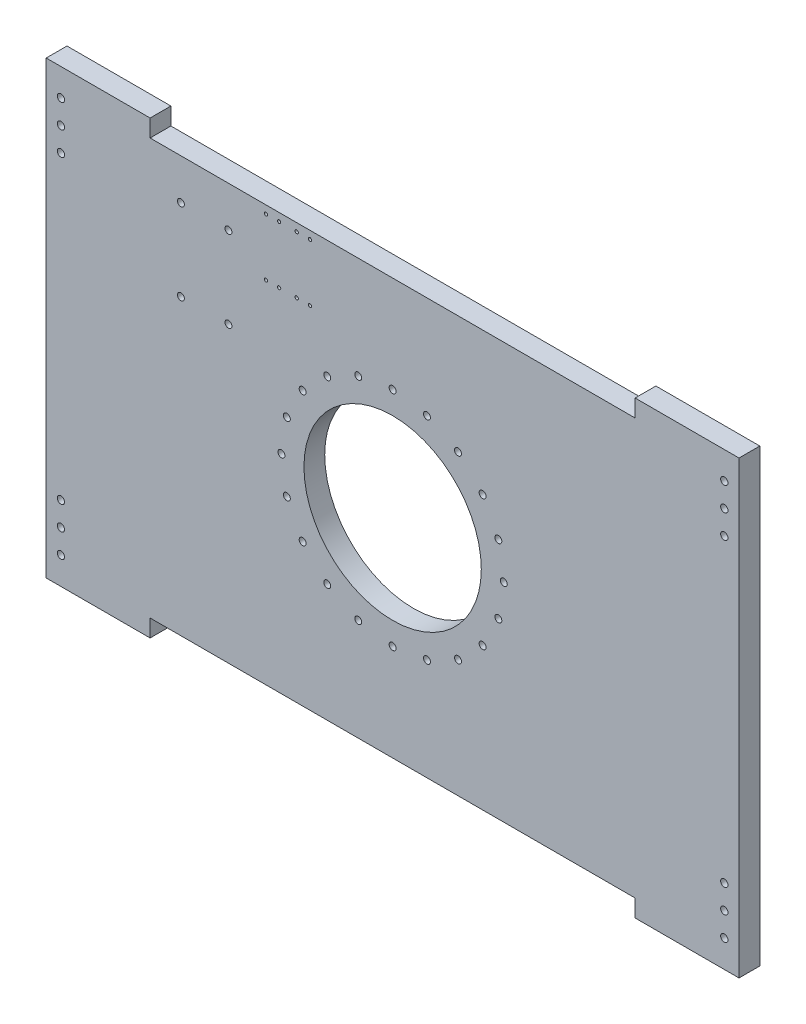
SolidWorks part; units mm, degrees
material "ASTM A36 Acier"
ref_plane "Plan de face" through (0, 0, 0) normal (0, 0, 1) x (1, 0, 0)
ref_plane "Plan de dessus" through (0, 0, 0) normal (0, 1, 0) x (1, 0, 0)
ref_plane "Plan de droite" through (0, 0, 0) normal (1, 0, 0) x (0, 0, -1)
sketch "Esquisse1" plane through (0, 0, 0) normal (0, 0, 1) x (1, 0, 0)
  line L0 (-1000, 1250) -> (-700, 1250)
  line L1 (-700, 1250) -> (-700, 1200)
  line L2 (-700, 1200) -> (700, 1200)
  line L3 (700, 1200) -> (700, 1250)
  line L4 (700, 1250) -> (1000, 1250)
  line L5 (1000, 1250) -> (1000, -50)
  line L6 (1000, -50) -> (700, -50)
  line L7 (700, -50) -> (700, 0)
  line L8 (700, 0) -> (-700, 0)
  line L9 (-700, 0) -> (-700, -50)
  line L10 (-700, -50) -> (-1000, -50)
  line L11 (-1000, -50) -> (-1000, 1250)
  point P15 (0, 0)
  dimension "D1" = 2000
  dimension "D2" = 50
  dimension "D4" = 300
  dimension "D5" = 300
  dimension "D6" = 300
  dimension "D7" = 300
  dimension "D8" = 1200
  dimension "D9" = 50
  dimension "D10" = 1400
extrude "Boss.-Extru.1" add sketch "Esquisse1" along normal blind 60
sketch "Esquisse2" plane through (0, 0, 60) normal (0, 0, 1) x (1, 0, 0)
  line L0 (700, -50) -> (1000, -50) construction
  circle A0 centre (0, 600) radius 256
  dimension "D1" = 512
  dimension "D2" = 650
extrude "Enlèv. mat.-Extru.1" cut sketch "Esquisse2" against normal through all
sketch "Esquisse4" plane through (0, 0, 0) normal (1, 0, 0) x (0, 0, -1)
  line L0 (0, 600) -> (1429.3387, 600) construction
  dimension "D1" = 600
sketch "Esquisse5" plane through (0, 0, 0) normal (0, 0, 1) x (1, 0, 0)
  circle A0 centre (0, 921) radius 10
  circle A1 centre (0, 600) radius 256 construction
  dimension "D1" = 20
  dimension "D2" = 321
extrude "Enlèv. mat.-Extru.3" cut sketch "Esquisse5" along normal through all
pattern_circular "Répétition circulaire1" count 20 every 18 about axis through (0, 600, 0) along (0, 0, -1) of "Enlèv. mat.-Extru.3"
ref_plane "Plan1" through (0, 0, 0) normal (0, 0, -1) x (-1, 0, 0)
sketch "Esquisse6" plane through (0, 0, 0) normal (0, 0, -1) x (-1, 0, 0)
  line L0 (1000, -50) -> (1000, 1250) construction
  line L1 (-1000, -50) -> (-1000, 1250) construction
  line L3 (0, 1100) -> (0, 0) construction
  line L5 (-700, -50) -> (-1000, -50) construction
  line L6 (994.9902, 600) -> (-1002.7622, 600) construction
  line L8 (700, 1200) -> (-700, 1200) construction
  circle A1 centre (-957.5, 28.75) radius 10.5
  circle A8 centre (-957.5, 1171.25) radius 10.5
  circle A9 centre (957.5, 1171.25) radius 10.5
  circle A14 centre (957.5, 28.75) radius 10.5
  circle A15 centre (-957.5, 97.5) radius 10.5
  circle A16 centre (-957.5, 166.25) radius 10.5
  circle A17 centre (-957.5, 1033.75) radius 10.5
  circle A18 centre (-957.5, 1102.5) radius 10.5
  circle A19 centre (957.5, 97.5) radius 10.5
  circle A20 centre (957.5, 166.25) radius 10.5
  circle A21 centre (957.5, 1102.5) radius 10.5
  circle A22 centre (957.5, 1033.75) radius 10.5
  point P5 (1000, 600)
  point P14 (0, 1200)
  dimension "D2" = 3
  dimension "D9" = 78.75
  dimension "21" = 21
  dimension "D10" = 42.5
extrude "Enlèv. mat.-Extru.4" cut sketch "Esquisse6" against normal through all
ref_plane "Plan2" through (-1000, -50, 60) normal (0, -1, 0) x (-1, 0, 0)
ref_plane "Plan7" through (-644.2059, 810, 60) normal (1, 0, 0) x (0, 0, -1)
sketch "Esquisse11" plane through (0, 0, 0) normal (0, 0, -1) x (-1, 0, 0)
  circle A0 centre (473.85, 847.5) radius 10
  circle A1 centre (611.15, 847.5) radius 10
  circle A2 centre (611.15, 1082.5) radius 10
  circle A3 centre (473.85, 1082.5) radius 10
extrude "Enlèv. mat.-Extru.5" cut sketch "Esquisse11" against normal blind 100 and the other way through all
sketch "Esquisse12" plane through (0, 0, 0) normal (0, 0, -1) x (-1, 0, 0)
  circle A0 centre (238.7481, 1177.1251) radius 4.7625
  circle A1 centre (327.6481, 1177.1251) radius 4.7625
  circle A2 centre (238.7481, 1012.0251) radius 4.7625
  circle A3 centre (276.8481, 1012.0251) radius 4.7625
  circle A4 centre (327.6481, 1012.0251) radius 4.7641
  circle A5 centre (365.7481, 1012.0251) radius 4.7625
  circle A6 centre (365.7481, 1177.1251) radius 4.7625
  circle A7 centre (276.8481, 1177.1251) radius 4.7625
extrude "Enlèv. mat.-Extru.6" cut sketch "Esquisse12" against normal blind 100
